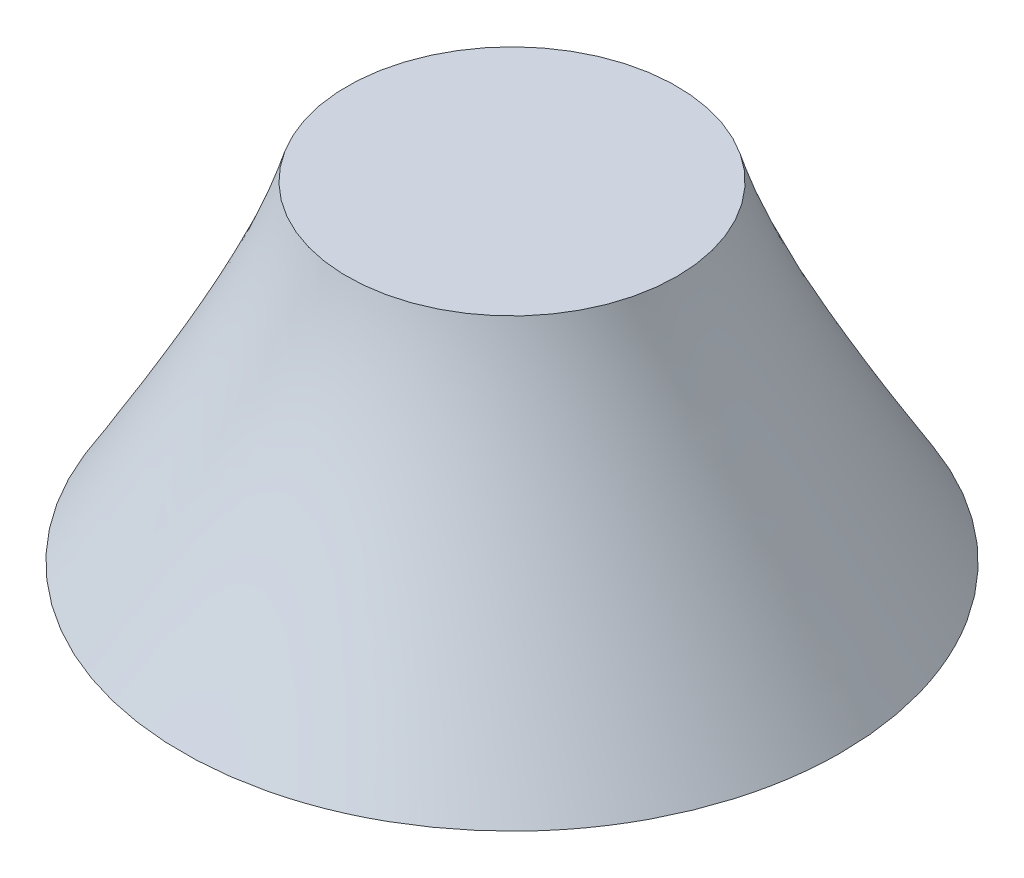
SolidWorks part; units mm, degrees
ref_plane "Спереди" through (0, 0, 0) normal (0, 0, 1) x (1, 0, 0)
ref_plane "Сверху" through (0, 0, 0) normal (0, 1, 0) x (1, 0, 0)
ref_plane "Справа" through (0, 0, 0) normal (1, 0, 0) x (0, 0, -1)
other "Configuration Table"
sketch "Эскиз3" plane through (0, 0, 0) normal (0, 1, 0) x (1, 0, 0)
  circle A0 centre (0, 0) radius 10
  dimension "D1" = 20
ref_plane "Плоскость1" through (0, 10, 0) normal (0, 1, 0) x (1, 0, 0)
sketch "Эскиз6" plane through (0, 10, 0) normal (0, 1, 0) x (1, 0, 0)
  circle A0 centre (0, 0) radius 5
  dimension "D1" = 10
loft "По сечениям1" add profiles "Эскиз6", "Эскиз3" connector at (-2.5127, 10, -4.3228) connector at (-9.2627, 0, -3.7687)
